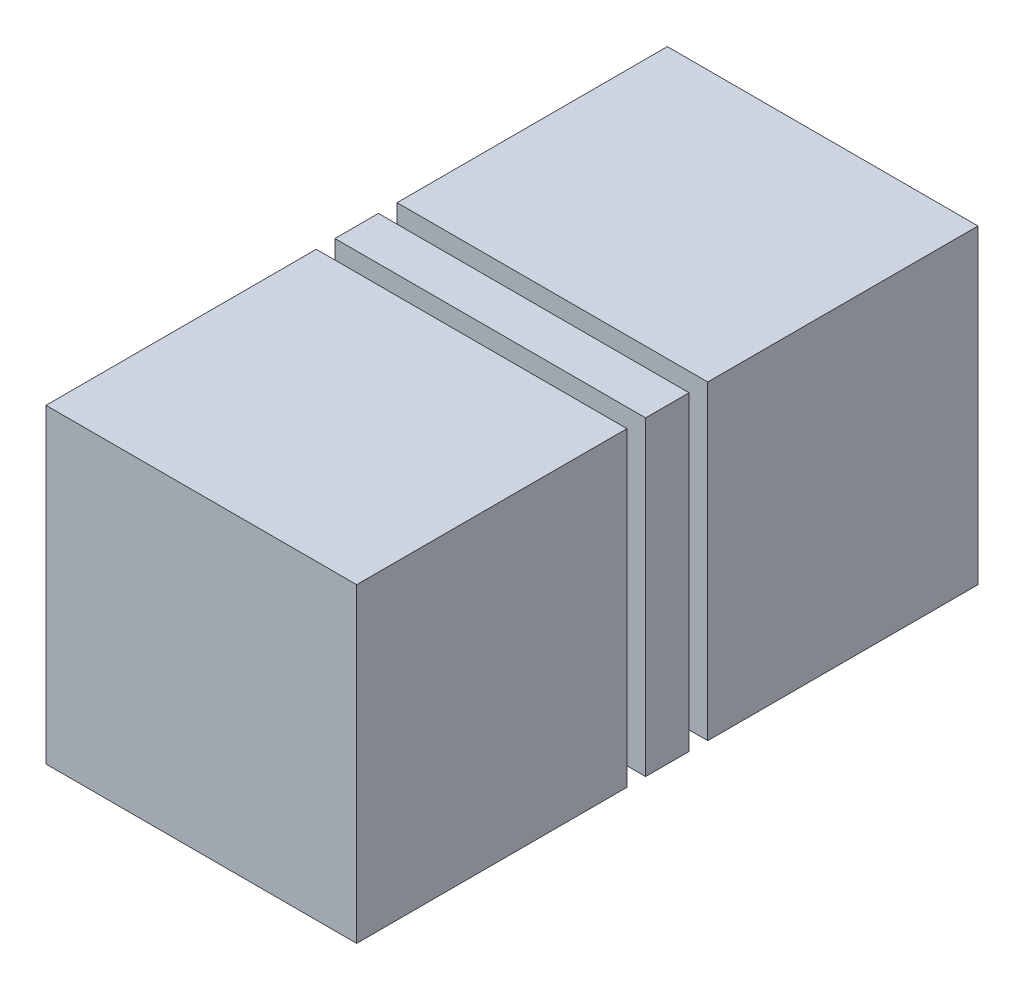
SolidWorks part; units mm, degrees
ref_plane "Front Plane" through (0, 0, 0) normal (0, 0, 1) x (1, 0, 0)
ref_plane "Top Plane" through (0, 0, 0) normal (0, 1, 0) x (1, 0, 0)
ref_plane "Right Plane" through (0, 0, 0) normal (1, 0, 0) x (0, 0, -1)
sketch "Sketch1" plane through (0, 0, 0) normal (1, 0, 0) x (0, 0, -1)
  line L1 (50, -25) -> (-50, -25)
  line L2 (50, -25) -> (50, 25)
  line L3 (50, 25) -> (-50, 25)
  line L4 (-50, -25) -> (-50, 25)
  line L5 (50, -25) -> (-50, 25) construction
  line L6 (50, 25) -> (-50, -25) construction
  point P0 (0, 0)
  dimension "D1" = 50
  dimension "D2" = 100
extrude "Boss-Extrude1" add sketch "Sketch1" along normal mid plane 50
ref_plane "Plane1" through (0, 0, 5) normal (0, 0, 1) x (1, 0, 0)
sketch "Sketch2" plane through (0, 0, 5) normal (0, 0, 1) x (1, 0, 0)
  line L10 (25, -25) -> (-25, -25) construction
  line L11 (25, 25) -> (25, -25) construction
  line L12 (25, 25) -> (-25, 25) construction
  line L13 (-25, 25) -> (-25, -25) construction
  line L14 (-22, 22) -> (-22, -22)
  line L15 (-22, -22) -> (22, -22)
  line L16 (22, -22) -> (22, 22)
  line L17 (22, 22) -> (-22, 22)
  line L18 (-22, 22) -> (-22, -22)
  line L19 (-22, -22) -> (22, -22)
  line L20 (22, -22) -> (22, 22)
  line L21 (22, 22) -> (-22, 22)
  line L22 (25, -25) -> (-25, -25)
  line L23 (25, 25) -> (25, -25)
  line L24 (25, 25) -> (-25, 25)
  line L25 (-25, 25) -> (-25, -25)
  dimension "D1" = 3
extrude "Cut-Extrude1" cut sketch "Sketch2" against normal mid plane 3
mirror "Mirror1" about plane through (0, 0, 0) normal (0, 0, 1) of "Cut-Extrude1"
shell "Shell1" thickness 5
